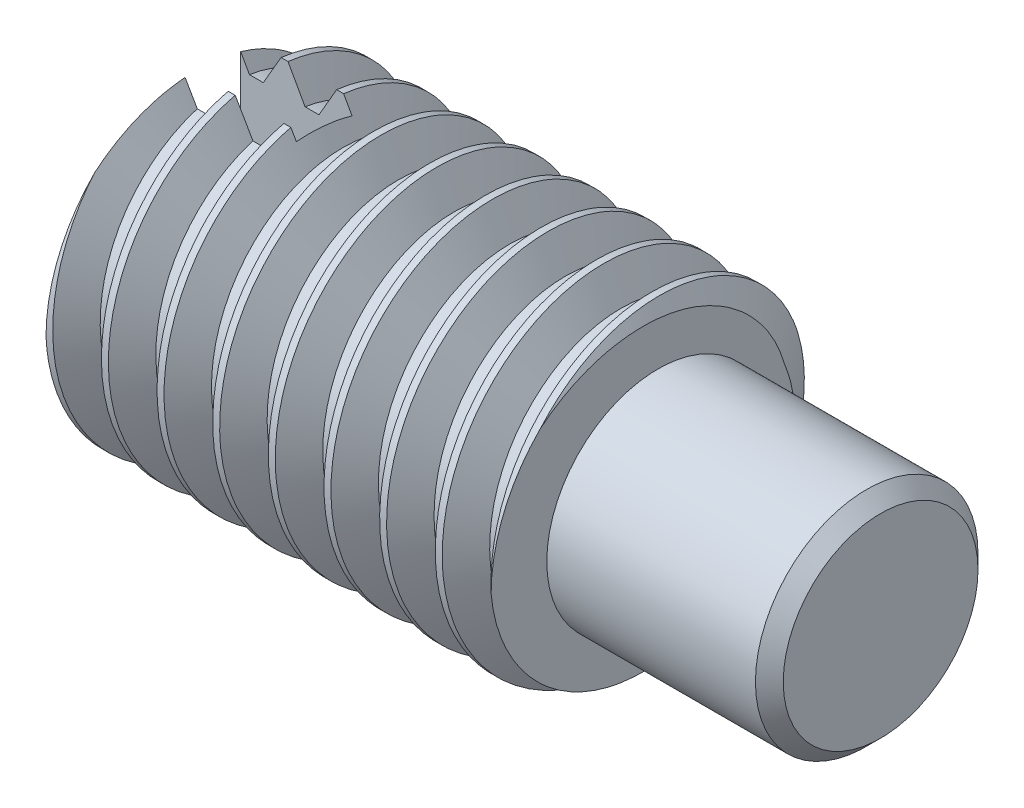
SolidWorks part; units mm, degrees
material "Alloy Steel"
ref_plane "Front Plane" through (0, 0, 0) normal (0, 0, 1) x (1, 0, 0)
ref_plane "Top Plane" through (0, 0, 0) normal (0, 1, 0) x (1, 0, 0)
ref_plane "Right Plane" through (0, 0, 0) normal (1, 0, 0) x (0, 0, -1)
sketch "Sketch1" plane through (0, 0, 0) normal (1, 0, 0) x (0, 0, -1)
  circle A0 centre (0, 0) radius 3
  circle A1 centre (0, 0) radius 2
  dimension "D1" = 6
  dimension "D2" = 4
extrude "Boss-Extrude1" add sketch "Sketch1" along normal blind 12 contours A1 region at (0, 0, 0)
extrude "Boss-Extrude2" add sketch "Sketch1<3>" along normal blind 8
sketch "Sketch1<3>" plane through (0, 0, 0) normal (1, 0, 0) x (0, 0, -1) same geometry as "Sketch1"
sketch "Sketch2" plane through (0, 0, 0) normal (-1, 0, 0) x (0, 0, 1)
  line L1 (-0.5, 3.3745) -> (0.5, 3.3745)
  line L2 (-0.5, 3.3745) -> (-0.5, -3.3745)
  line L3 (-0.5, -3.3745) -> (0.5, -3.3745)
  line L4 (0.5, 3.3745) -> (0.5, -3.3745)
  line L5 (-0.5, 3.3745) -> (0.5, -3.3745) construction
  line L6 (-0.5, -3.3745) -> (0.5, 3.3745) construction
  point P0 (0, 0)
  dimension "D1" = 1
extrude "Cut-Extrude1" cut sketch "Sketch2" against normal blind 2
thread "Thread1" pitch 1 method cut profile "Thread Profile1" start angle 0, offset 1, length 10, pitch 1, diameter 6
ref_plane "Plane1" through (9, 0, 3) normal (0, -1, 0) x (0, 0, 1)
sketch "Thread Profile1" plane through (9, 0, 3) normal (0, -1, 0) x (0, 0, 1)
  line L0 (0, 0) -> (0, 1) construction
  line L11 (0, 0) -> (0, 0.875)
  line L12 (0, 0.875) -> (-0.5413, 0.5625)
  line L13 (-0.5413, 0.5625) -> (-0.5413, 0.3125)
  line L15 (-0.5413, 0.3125) -> (0, 0)
  line L17 (-0.5413, 0.4375) -> (0, 0.4375) construction
  point P2 (0, 0)
  dimension "Pitch" = 1
  dimension "Profile_Angle" = 60
  dimension "Profile_Land" = 0.25
  dimension "Profile_Height" = 0.5413
chamfer "Chamfer1" distance 0.25 angle 45 1 edges at (12, 0, -2)
